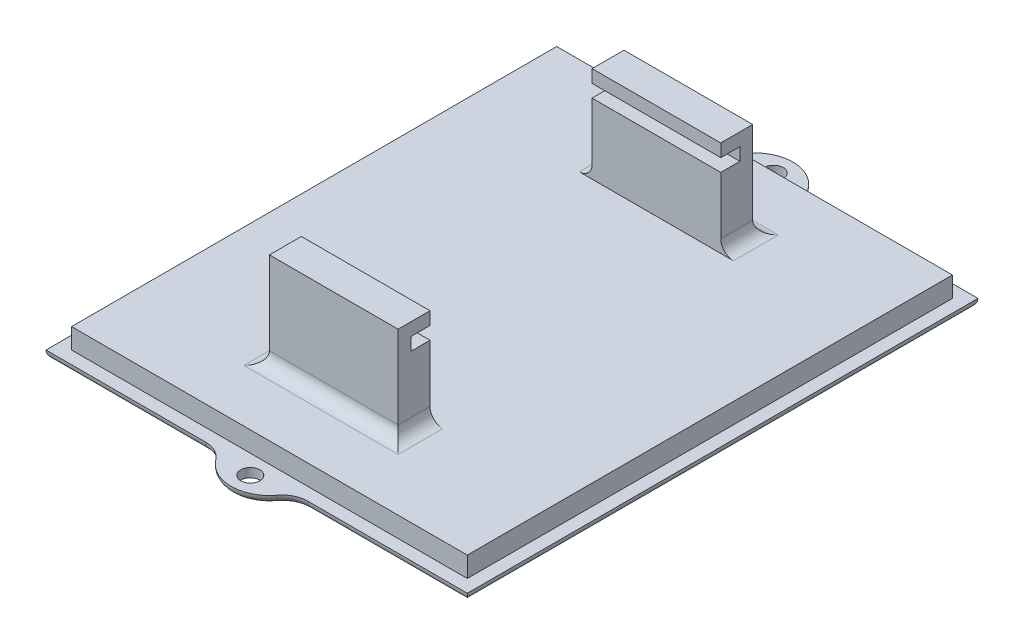
SolidWorks part; units mm, degrees
ref_plane "Front Plane" through (0, 0, 0) normal (0, 0, 1) x (1, 0, 0)
ref_plane "Top Plane" through (0, 0, 0) normal (0, 1, 0) x (1, 0, 0)
ref_plane "Right Plane" through (0, 0, 0) normal (1, 0, 0) x (0, 0, -1)
sketch "Sketch1" plane through (0, 0, 0) normal (0, 1, 0) x (1, 0, 0)
  line L0 (-31, 38) -> (31, 38)
  line L5 (-31, 38) -> (-31, -38)
  line L6 (-31, -38) -> (31, -38)
  line L7 (31, 38) -> (31, -38)
  point P11 (-31, 0)
  point P12 (0, -38)
  dimension "D3" = 76
  dimension "D4" = 62
extrude "Boss-Extrude1" add sketch "Sketch1" along normal blind 4.575
sketch "Sketch11" plane through (0, 0, 0) normal (0, -1, 0) x (-1, 0, 0)
  line L0 (-31, 38) -> (31, 38) construction
  line L1 (-33, -40) -> (33, -40)
  line L2 (-33, -40) -> (-33, 40)
  line L3 (-33, 40) -> (33, 40)
  line L4 (33, -40) -> (33, 40)
  line L5 (-31, -38) -> (-31, 38) construction
  line L6 (31, -38) -> (-31, -38) construction
  line L13 (31, 38) -> (31, -38) construction
  dimension "D1" = 2
  dimension "D2" = 2
  dimension "D3" = 2
  dimension "D4" = 2
extrude "Boss-Extrude5" add sketch "Sketch11" against normal blind 1.4
sketch "Sketch4" plane through (0, 0, 0) normal (0, 1, 0) x (1, 0, 0)
  line L2 (-31, -38) -> (31, -38) construction
  line L3 (33, -40) -> (-33, -40) construction
  line L5 (-8, -40) -> (8, -40)
  arc A3 (-8, -40) -> (-4.8, -41.6) centre (-8, -44) cw
  arc A4 (-4.8, -41.6) -> (4.8, -41.6) centre (0, -38) ccw
  arc A5 (4.8, -41.6) -> (8, -40) centre (8, -44) cw
  dimension "D1" = 6
  dimension "D4" = 4
extrude "Boss-Extrude3" add sketch "Sketch4" along normal blind 1.4
sketch "Sketch12" plane through (0, 1.4, 0) normal (0, 1, 0) x (1, 0, 0)
  line L0 (0, -38) -> (0, -44) construction
  line L1 (-31, -38) -> (31, -38) construction
  arc A0 (-4.8, -41.6) -> (4.8, -41.6) centre (0, -38) ccw construction
  circle A1 centre (0, -41) radius 1.5
  dimension "D1" = 3
extrude "Cut-Extrude3" cut sketch "Sketch12" against normal up to next
mirror "Mirror1" about plane through (0, 0, 0) normal (0, 0, 1) of "Cut-Extrude3", "Boss-Extrude3"
fillet "Fillet1" radius 1.4 12 edges at (20.5, 0, -40) (6.2111, 0, -40.4223) (0, 0, -44) (-6.2111, 0, -40.4223) (-20.5, 0, -40) (-33, 0, 0) (-20.5, 0, 40) (-6.2111, 0, 40.4223) (0, 0, 44) (6.2111, 0, 40.4223) (20.5, 0, 40) (33, 0, 0)
sketch "Sketch5" plane through (0, 4.575, 0) normal (0, 1, 0) x (1, 0, 0)
  line L0 (-15, 0) -> (15, 0) construction
  text T0 "MicroBit" font "Arial Narrow" height in points 24
  point P6 (0, 0)
  dimension "D1" = 30
extrude "Letters" [suppressed] cut sketch "Sketch5" against normal blind 2
sketch "Sketch21" plane through (0, 4.575, 0) normal (0, 1, 0) x (1, 0, 0)
  line L1 (-21.1498, 24.9347) -> (20.8502, 24.9347)
  line L2 (-21.1498, 24.9347) -> (-21.1498, -26.5653)
  line L3 (-21.1498, -26.5653) -> (20.8502, -26.5653)
  line L4 (20.8502, 24.9347) -> (20.8502, -26.5653)
  line L5 (-21.1498, 24.9347) -> (20.8502, -26.5653) construction
  line L6 (-21.1498, -26.5653) -> (20.8502, 24.9347) construction
  line L7 (-10.2291, -22.7722) -> (9.9294, -22.7722)
  line L8 (-10.2291, -22.7722) -> (-10.2291, -27.7722)
  line L9 (-10.2291, -27.7722) -> (9.9294, -27.7722)
  line L10 (9.9294, -22.7722) -> (9.9294, -27.7722)
  line L11 (-10.2291, -22.7722) -> (9.9294, -27.7722) construction
  line L12 (-10.2291, -27.7722) -> (9.9294, -22.7722) construction
  point P4 (-0.1498, -0.8153)
  point P9 (-0.1498, -25.2722)
  dimension "D1" = 42
  dimension "D2" = 51.5
  dimension "D3" = 5
extrude "Boss-Extrude8" add sketch "Sketch21" along normal blind 15 contours L9 L10 L7 L8
sketch "Sketch33" plane through (9.9294, 0, 0) normal (1, 0, 0) x (0, 0, -1)
  line L0 (-22.7722, 19.575) -> (-22.7722, 4.575) construction
  line L1 (-22.7722, 17.575) -> (-25.7722, 17.575)
  line L2 (-22.7722, 17.575) -> (-22.7722, 15.575)
  line L3 (-22.7722, 15.575) -> (-25.7722, 15.575)
  line L4 (-25.7722, 17.575) -> (-25.7722, 15.575)
  line L5 (-22.7722, 17.575) -> (-25.7722, 15.575) construction
  line L6 (-22.7722, 15.575) -> (-25.7722, 17.575) construction
  line L7 (-22.7722, 4.575) -> (-27.7722, 4.575) construction
  point P4 (-24.2722, 16.575)
  dimension "D1" = 2
  dimension "D2" = 3
  dimension "D3" = 11
extrude "Cut-Extrude7" cut sketch "Sketch33" against normal blind 25
mirror "Mirror2" about plane through (0, 0, 0) normal (0, 0, 1) of "Cut-Extrude7", "Boss-Extrude8"
fillet "Fillet2" radius 2 6 edges at (9.9294, 4.575, 25.2722) (-10.2291, 4.575, 25.2722) (-0.1498, 4.575, 27.7722) (-10.2291, 4.575, -25.2722) (-0.1498, 4.575, -27.7722) (9.9294, 4.575, -25.2722)
